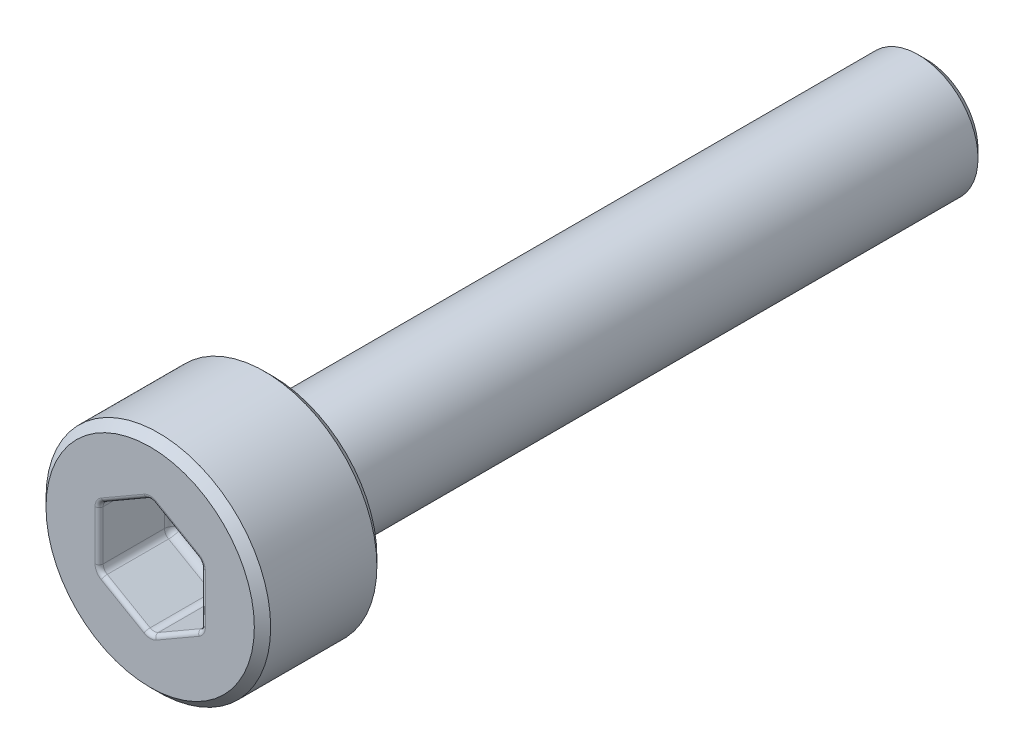
SolidWorks part; units mm, degrees
material "1.4000 (X6Cr13)"
ref_plane "Ebene vorne" through (0, 0, 0) normal (0, 0, 1) x (1, 0, 0)
ref_plane "Ebene oben" through (0, 0, 0) normal (0, 1, 0) x (1, 0, 0)
ref_plane "Ebene rechts" through (0, 0, 0) normal (1, 0, 0) x (0, 0, -1)
sketch "Skizze1" plane through (0, 0, 0) normal (1, 0, 0) x (0, 0, -1)
  line L0 (-21.9199, 0) -> (33.7608, 0) construction
  line L1 (0, 13.9907) -> (0, -9.4798) construction
  line L2 (-3, 0) -> (-3, 2.75)
  line L3 (-3, 2.75) -> (0, 2.75)
  line L4 (0, 2.75) -> (0, 1.465)
  line L5 (0, 1.465) -> (16, 1.465)
  line L6 (16, 1.465) -> (16, 0)
  line L7 (16, 0) -> (-3, 0)
  dimension "D1" = 2.93
  dimension "D2" = 3
  dimension "D3" = 5.5
  dimension "D4" = 16
revolve "Rotation1" add sketch "Skizze1" angle 360 about L0
sketch "Skizze2" plane through (0, 0, 3) normal (0, 0, 1) x (1, 0, 0)
  line L0 (0, 8.6995) -> (0, -7.3778) construction
  line L1 (1.25, -0.7217) -> (1.25, 0.7217)
  line L2 (1.25, 0.7217) -> (0, 1.4434)
  line L3 (0, 1.4434) -> (-1.25, 0.7217)
  line L4 (-1.25, 0.7217) -> (-1.25, -0.7217)
  line L5 (-1.25, -0.7217) -> (0, -1.4434)
  line L6 (0, -1.4434) -> (1.25, -0.7217)
  circle A0 centre (0, 0) radius 1.25 construction
  dimension "D1" = 2.5
extrude "Schnitt-Linear austragen1" cut sketch "Skizze2" against normal blind 1.8
chamfer "Fase1" distance 0.2 angle 45 3 edges at (2.75, 0, 3) (2.75, 0, 0) (1.465, 0, -16)
fillet "Verrundung1" radius 0.2 13 edges at (-0.625, -1.0825, 1.2) (-1.25, 0, 1.2) (-0.625, 1.0825, 1.2) (0.625, 1.0825, 1.2) (1.25, 0, 1.2) (0.625, -1.0825, 1.2) (-1.25, -0.7217, 2.1) (0, -1.4434, 2.1) (1.25, -0.7217, 2.1) (1.25, 0.7217, 2.1) (0, 1.4434, 2.1) (-1.25, 0.7217, 2.1) (1.465, 0, 0)
fillet "Verrundung2" radius 0.1 12 edges at (1.2232, -0.7062, 3) (0.625, -1.0825, 3) (0, -1.4124, 3) (-0.625, -1.0825, 3) (-1.2232, -0.7062, 3) (-1.25, 0, 3) (-1.2232, 0.7062, 3) (-0.625, 1.0825, 3) (0, 1.4124, 3) (0.625, 1.0825, 3) (1.2232, 0.7062, 3) (1.25, 0, 3)
ref_axis "Achse1" through (0, 0, -19.6323) along (0, 0, 1)
